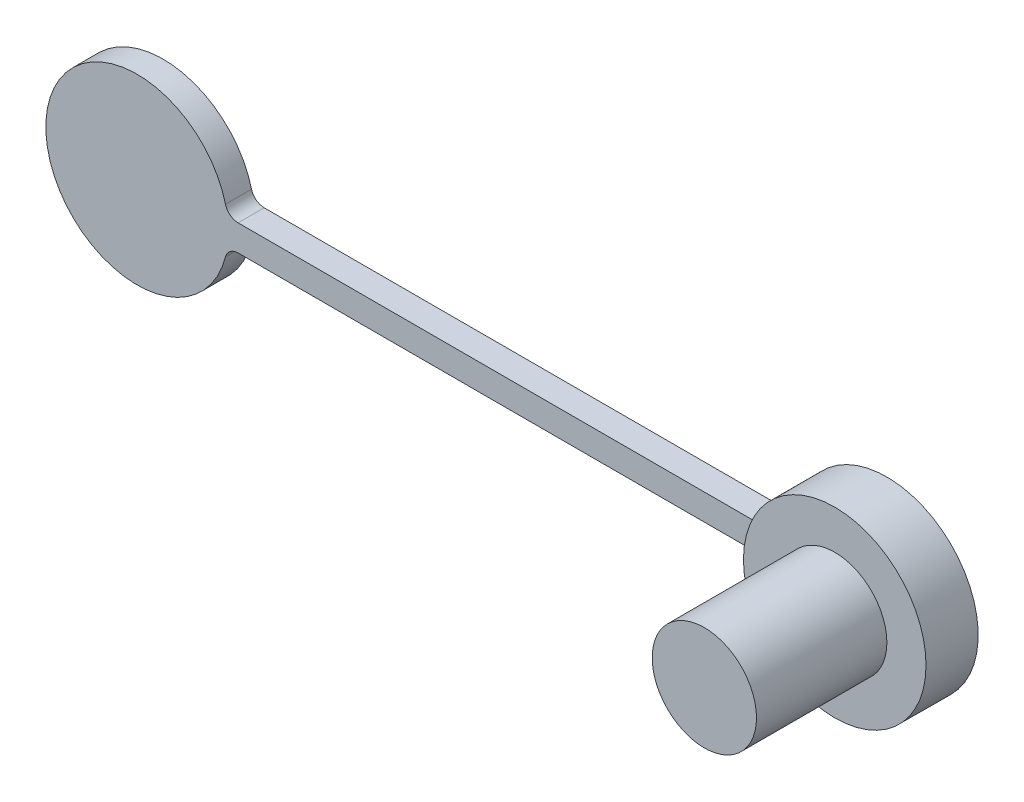
SolidWorks part; units mm, degrees
ref_plane "Plano frontal" through (0, 0, 0) normal (1, 0, 0) x (0, 1, 0)
ref_plane "Plano superior" through (0, 0, 0) normal (0, 0, 1) x (0, 1, 0)
ref_plane "Plano direito" through (0, 0, 0) normal (0, 1, 0) x (-1, 0, 0)
sketch "Esboço1" plane through (0, 0, 0) normal (0, 0, 1) x (0, 1, 0)
  circle A0 centre (0, 0) radius 35
extrude "Ressalto-extrusão1" add sketch "Esboço1" along normal blind 10
sketch "Esboço4" plane through (0, 0, 0) normal (1, 0, 0) x (0, 1, 0)
  line L0 (-35, 0) -> (35, 0) construction
  line L1 (-5, 10) -> (5, 10)
  line L2 (-5, 10) -> (-5, 0)
  line L3 (-5, 0) -> (5, 0)
  line L4 (5, 10) -> (5, 0)
  line L5 (-5, 10) -> (5, 0) construction
  line L6 (-5, 0) -> (5, 10) construction
  line L9 (35, 10) -> (-35, 10) construction
  point P0 (0, 5)
  point P7 (-50.681, -21.7671)
  point P9 (0, 4.9602)
  point P10 (0, 5)
  point P12 (0, 5)
  point P13 (0, 0)
  point P14 (10.0225, 10)
  dimension "D1" = 10
extrude "Ressalto-extrusão2" add sketch "Esboço4" along normal blind 277.5
fillet "Filete3" radius 5 1 edges at (34.641, -5, 5)
fillet "Filete4" radius 5 1 edges at (34.641, 5, 5)
sketch "Esboço6" plane through (0, 0, 10) normal (0, 0, 1) x (1, 0, 0)
  line L0 (277.5, 5) -> (277.5, -5) construction
  circle A0 centre (277.5, 0) radius 35
extrude "Ressalto-extrusão3" add sketch "Esboço6" against normal blind 10 and the other way blind 10
fillet "Filete5" radius 5 1 edges at (242.859, -5, 5)
fillet "Filete6" radius 5 1 edges at (242.859, 5, 5)
sketch "Esboço7" plane through (0, 0, 20) normal (0, 0, 1) x (1, 0, 0)
  circle A0 centre (277.5, 0) radius 20
extrude "Ressalto-extrusão4" add sketch "Esboço7" along normal blind 50
